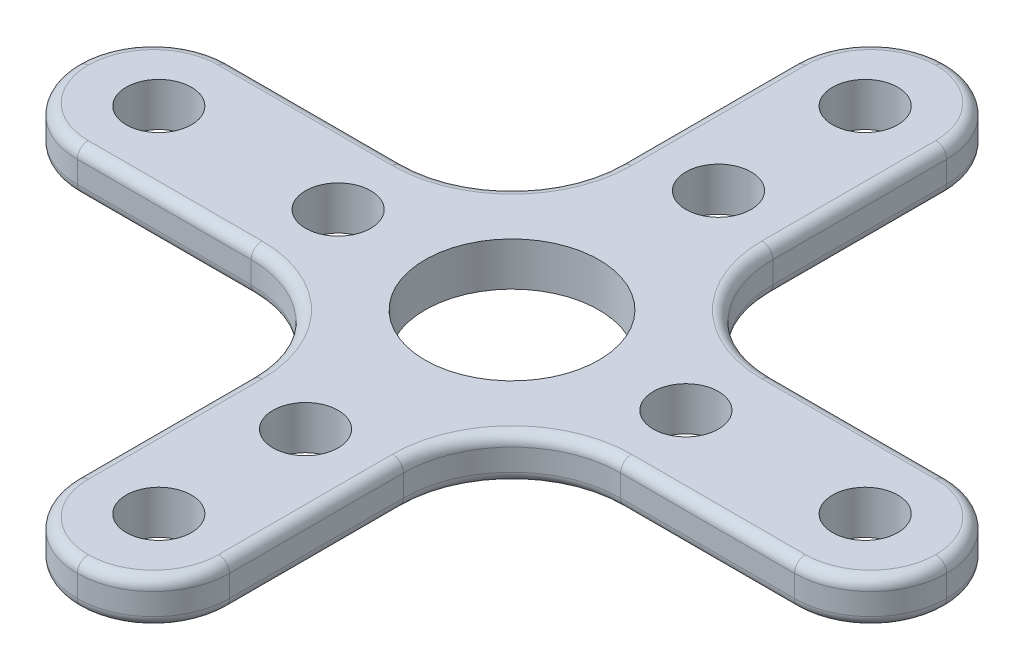
SolidWorks part; units mm, degrees
ref_plane "Front Plane" through (0, 0, 0) normal (0, 0, 1) x (1, 0, 0)
ref_plane "Top Plane" through (0, 0, 0) normal (0, 1, 0) x (1, 0, 0)
ref_plane "Right Plane" through (0, 0, 0) normal (1, 0, 0) x (0, 0, -1)
sketch "Sketch1" plane through (0, 0, 0) normal (0, 1, 0) x (1, 0, 0)
  line L0 (0, -20) -> (0, 20)
  line L1 (-3.5, 20) -> (3.5, 20)
  line L2 (-3.5, 20) -> (-3.5, -20)
  line L3 (-3.5, -20) -> (3.5, -20)
  line L4 (3.5, 20) -> (3.5, -20)
  line L5 (-3.5, 20) -> (3.5, -20) construction
  line L6 (-3.5, -20) -> (3.5, 20) construction
  line L7 (-20, 3.5) -> (20, 3.5)
  line L8 (-20, 3.5) -> (-20, -3.5)
  line L9 (-20, -3.5) -> (20, -3.5)
  line L10 (20, 3.5) -> (20, -3.5)
  line L11 (-20, 3.5) -> (20, -3.5) construction
  line L12 (-20, -3.5) -> (20, 3.5) construction
  line L13 (-20, 0) -> (20, 0)
  circle A1 centre (0, 16.25) radius 1.5
  circle A2 centre (0, 9.5) radius 1.5
  circle A3 centre (0, -9.5) radius 1.5
  circle A4 centre (0, -16.25) radius 1.5
  circle A5 centre (-16.25, 0) radius 1.5
  circle A6 centre (-8, 0) radius 1.5
  circle A7 centre (8, 0) radius 1.5
  circle A8 centre (16.25, 0) radius 1.5
  point P0 (0, 0)
  point P6 (0, 0)
  dimension "D3" = 3
  dimension "D4" = 3
  dimension "D13" = 3
  dimension "D14" = 3
  dimension "D15" = 3
  dimension "D16" = 3
  dimension "D17" = 3
  dimension "D18" = 3
  dimension "D1" = 40
  dimension "D2" = 7
  dimension "D5" = 9.5
  dimension "D6" = 16.25
  dimension "D7" = 16.25
  dimension "D8" = 16.25
  dimension "D9" = 16.25
  dimension "D10" = 9.5
  dimension "D11" = 8
  dimension "D12" = 8
extrude "Boss-Extrude1" add sketch "Sketch1" along normal blind 2 contours A6 L13 L2 L7 L8 A5 | A6 L13 A5 L8 L9 L2 | A2 L0 A1 L1 L2 L7 | A2 L0 L7 L4 L1 A1 | A8 L13 L10 L7 L4 A7 | L2 L13 L0 L7 | L13 L2 L9 L0 | L13 L0 L9 L4 | L0 L13 L4 L7 | A4 L0 A3 L9 L2 L3 | A4 L0 L3 L4 L9 A3 | A8 L13 A7 L4 L9 L10 region at (-1.9053, 0, 11.5931) region at (1.9053, 0, 11.5931) region at (-11.6977, 0, 1.9053) region at (-1.75, 0, 1.75) region at (1.75, 0, 1.75) region at (11.6977, 0, 1.9053) region at (-11.6977, 0, -1.9053) region at (-1.75, 0, -1.75) region at (1.75, 0, -1.75) region at (11.6977, 0, -1.9053) region at (-1.9053, 0, -11.5931) region at (1.9053, 0, -11.5931)
fillet "Fillet1" radius 5 4 edges at (-3.5, 1, -3.5) (3.5, 1, -3.5) (3.5, 1, 3.5) (-3.5, 1, 3.5)
fillet "Fillet2" radius 3.5 8 edges at (20, 1, 3.5) (20, 1, -3.5) (3.5, 1, -20) (-3.5, 1, -20) (-20, 1, -3.5) (-20, 1, 3.5) (3.5, 1, 20) (-3.5, 1, 20)
sketch "Sketch2" plane through (0, 2, 0) normal (0, 1, 0) x (1, 0, 0)
  circle A0 centre (0, 0) radius 4
  dimension "D1" = 8
extrude "Cut-Extrude1" cut sketch "Sketch2" against normal up to next
fillet "Fillet3" radius 0.5 40 edges at (-12.5, 0, -3.5) (-18.9749, 0, -2.4749) (-18.9749, 0, 2.4749) (-12.5, 0, 3.5) (-4.9645, 0, 4.9645) (-3.5, 0, 12.5) (-2.4749, 0, 18.9749) (2.4749, 0, 18.9749) (3.5, 0, 12.5) (4.9645, 0, 4.9645) (12.5, 0, 3.5) (18.9749, 0, 2.4749) (18.9749, 0, -2.4749) (12.5, 0, -3.5) (4.9645, 0, -4.9645) (3.5, 0, -12.5) (2.4749, 0, -18.9749) (-2.4749, 0, -18.9749) (-3.5, 0, -12.5) (-2.4749, 2, -18.9749) (2.4749, 2, -18.9749) (3.5, 2, -12.5) (4.9645, 2, -4.9645) (12.5, 2, -3.5) (18.9749, 2, -2.4749) (18.9749, 2, 2.4749) (12.5, 2, 3.5) (4.9645, 2, 4.9645) (3.5, 2, 12.5) (2.4749, 2, 18.9749) (-2.4749, 2, 18.9749) (-3.5, 2, 12.5) (-4.9645, 2, 4.9645) (-12.5, 2, 3.5) (-18.9749, 2, 2.4749) (-18.9749, 2, -2.4749) (-12.5, 2, -3.5) (-4.9645, 2, -4.9645) (-4.9645, 0, -4.9645) (-3.5, 2, -12.5)
